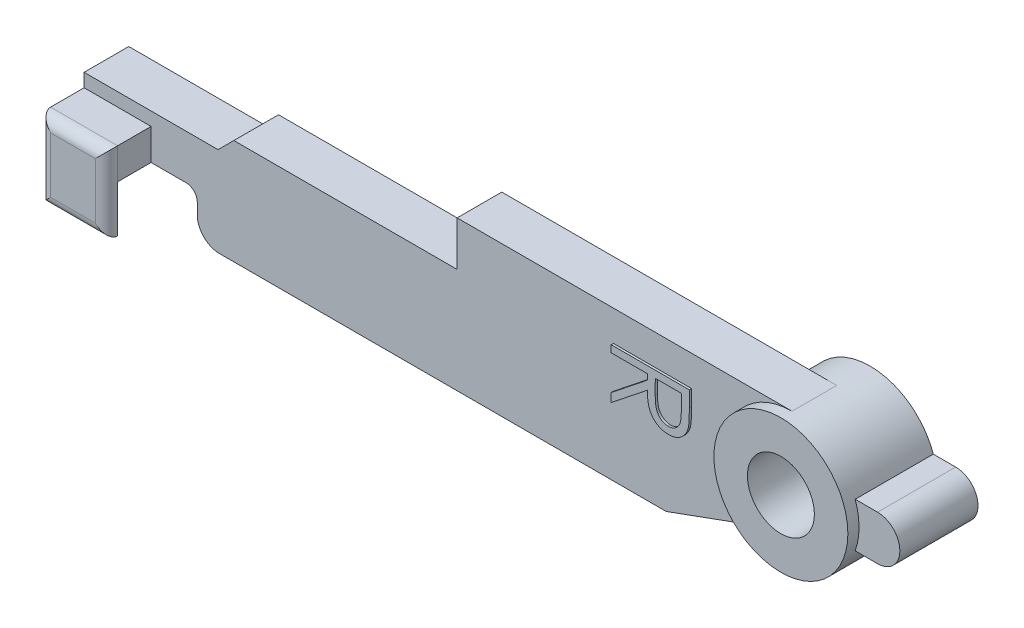
SolidWorks part; units mm, degrees
ref_plane "Piano frontale" through (0, 0, 0) normal (0, 0, 1) x (1, 0, 0)
ref_plane "Piano superiore" through (0, 0, 0) normal (0, 1, 0) x (1, 0, 0)
ref_plane "Piano destro" through (0, 0, 0) normal (1, 0, 0) x (0, 0, -1)
sketch "Schizzo1" plane through (0, 0, 0) normal (0, 0, 1) x (1, 0, 0)
  line L0 (19.0188, 0) -> (-19.0188, 0) construction
  line L1 (0, 0) -> (0, 8.6004) construction
  line L2 (-16.7071, 0.2929) -> (-10.7071, 0.2929)
  line L3 (-10.7071, 0.2929) -> (-10, 1)
  line L4 (-10, 1) -> (0, 1)
  line L5 (0, 1) -> (0, 3)
  line L6 (0, 3) -> (15, 3)
  line L7 (15, 3) -> (15, 0)
  line L8 (15, 0) -> (15, -1.655)
  line L9 (15, -1.655) -> (9.3618, -3.7071)
  line L10 (9.3618, -3.7071) -> (-11.6382, -3.7071)
  line L11 (-11.6382, -3.7071) -> (-11.6382, -1.7071)
  line L12 (-11.6382, -1.7071) -> (-16.7071, -1.7071)
  line L13 (-16.7071, -1.7071) -> (-16.7071, 0.2929)
  point P4 (0, 0)
  dimension "D1" = 15
  dimension "D2" = 10
  dimension "D3" = 6
  dimension "D4" = 1
  dimension "D5" = 2
  dimension "D6" = 6
  dimension "D7" = 20
  dimension "D8" = 21
  dimension "D9" = 3
  dimension "D10" = 45
  dimension "D11" = 2
  dimension "D12" = 2
extrude "Estrusione-Estrusione1" add sketch "Schizzo1" along normal blind 2
fillet "Raccordo1" radius 1 1 edges at (-11.6382, -3.7071, 1)
fillet "Raccordo2" radius 0.5 1 edges at (-11.6382, -1.7071, 1)
sketch "Schizzo2" plane through (0, 0, 0) normal (0, 0, 1) x (1, 0, 0)
  line L0 (-10.7071, 0.2929) -> (22.9117, 0.2929) construction
  line L1 (15, -1.655) -> (15, 3) construction
  line L2 (15, 3) -> (0, 3) construction
  circle A0 centre (15, 0) radius 3
  dimension "D1" = 6
extrude "Estrusione-Estrusione2" add sketch "Schizzo2" along direction (0, 0, -1) on the side of the normal blind 2.5 and the other way blind 1.5
sketch "Schizzo3" plane through (0, 0, 0) normal (0, 0, 1) x (1, 0, 0)
  line L0 (15, 0) -> (16.6892, 0) construction
  line L1 (18.8284, 1) -> (17.8284, 1)
  line L4 (18.8284, -1) -> (17.8284, -1)
  line L5 (18.8284, 1) -> (18.8284, 0) construction
  arc A1 (18.8284, -1) -> (18.8284, 1) centre (18.8284, 0) ccw
  circle A2 centre (15, 0) radius 3 construction
  arc A3 (17.8284, -1) -> (17.8284, 1) centre (15, 0) ccw
  dimension "D2" = 1
  dimension "D3" = 1
  dimension "D4" = 1
extrude "Estrusione-Estrusione3" add sketch "Schizzo3" along normal up to surface and the other way up to surface up to face at (-4.9758, -0.6872, 2) other way up to face at (18, 0, -1.5)
sketch "Schizzo4" plane through (-16.7071, 0, 0) normal (-1, 0, 0) x (0, 0, 1)
  line L0 (2, -1.7071) -> (3.5, -1.7071)
  line L1 (3.5, -1.7071) -> (3.5, -3.8071)
  line L2 (3.5, -3.8071) -> (4, -3.8071)
  line L3 (4, -3.8071) -> (4, -0.3071)
  line L4 (4, -0.3071) -> (2, -0.3071)
  line L5 (2, 0.2929) -> (2, -1.7071) construction
  line L6 (2, -0.3071) -> (2, -1.7071)
  line L9 (0, 0.2929) -> (0, -1.7071) construction
  dimension "D1" = 1.4
  dimension "D2" = 3.5
  dimension "D3" = 0.5
  dimension "D4" = 4
extrude "Estrusione-Estrusione4" add sketch "Schizzo4" against normal blind 3
fillet "Raccordo3" radius 0.5 4 edges at (-15.2071, -0.3071, 4) (-13.7071, -2.0571, 4) (-15.2071, -3.8071, 4) (-16.7071, -2.0571, 4)
sketch "Schizzo5" plane through (0, 0, 2.5) normal (0, 0, 1) x (1, 0, 0)
  circle A0 centre (15, 0) radius 1.5
  circle A1 centre (15, 0) radius 3 construction
  dimension "D1" = 1.5
extrude "Taglio-Estrusione1" cut sketch "Schizzo5" against normal through all
sketch "Schizzo6" plane through (0, 0, 2) normal (0, 0, 1) x (1, 0, 0)
  line L0 (7, 2.0786) -> (7, -1.5963) construction
  line L1 (0, 3) -> (0, 1) construction
  text T0 "R"
  dimension "D1" = 7
extrude "Estrusione-Estrusione5" add sketch "Schizzo6" along normal blind 0.1
sketch "Schizzo7" plane through (0, 0, 0) normal (0, 0, -1) x (-1, 0, 0)
  line L0 (13.7071, -0.3071) -> (16.7071, -0.3071) construction
  line L1 (16.7071, -0.3071) -> (13.7071, -0.3071) construction
  line L2 (16.7071, -0.3071) -> (16.7071, -1.7071) construction
  line L3 (16.7071, -1.7071) -> (13.7071, -1.7071) construction
  line L4 (13.7071, -0.3071) -> (13.7071, -1.7071) construction
  line L5 (16.7071, -0.3071) -> (13.7071, -1.7071) construction
  line L6 (16.7071, -1.7071) -> (13.7071, -0.3071) construction
  line L7 (13.7071, -0.3071) -> (16.7071, -0.3071)
  point P4 (15.2071, -1.0071)
ref_axis "Assi1" through (-15.2071, -1.0071, 0) along (0, 0, 1)
